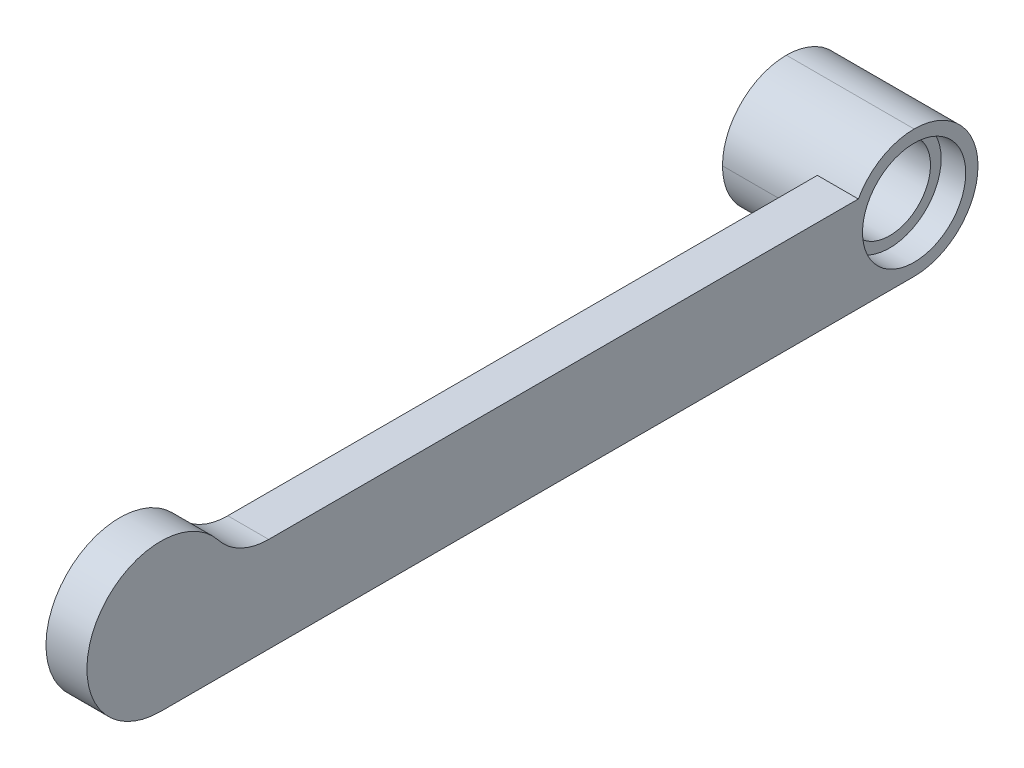
SolidWorks part; units mm, degrees
ref_plane "前视基准面" through (0, 0, 0) normal (0, 0, 1) x (1, 0, 0)
ref_plane "上视基准面" through (0, 0, 0) normal (0, 1, 0) x (1, 0, 0)
ref_plane "右视基准面" through (0, 0, 0) normal (1, 0, 0) x (0, 0, -1)
other "Configuration Table"
sketch "草图1" plane through (0, 0, 0) normal (1, 0, 0) x (0, 0, -1)
  line L0 (46, 3.3) -> (46, -4.5) construction
  line L1 (0, -4.5) -> (49.9, -4.5)
  line L2 (0, -4.5) -> (0, 3.3)
  line L3 (0, 3.3) -> (49.9, 3.3)
  line L4 (49.9, -4.5) -> (49.9, 3.3)
  line L6 (42.1, -4.5) -> (49.9, -4.5)
  line L7 (42.1, -4.5) -> (42.1, 3.3)
  line L8 (42.1, 3.3) -> (49.9, 3.3)
  line L9 (49.9, -4.5) -> (49.9, 3.3)
  line L10 (42.1, -4.5) -> (49.9, 3.3) construction
  line L11 (42.1, 3.3) -> (49.9, -4.5) construction
  circle A4 centre (0, 0) radius 1.8
  circle A5 centre (0, 0) radius 4.5
  circle A6 centre (46, -0.6) radius 2.5
  circle A7 centre (46, -0.6) radius 3.15
  circle A8 centre (0, 0) radius 0.25
  point P9 (46, -0.6)
  dimension "D1" = 3.6
  dimension "D4" = 46
  dimension "D5" = 3.9
  dimension "D2" = 9
  dimension "D6" = 5
  dimension "D7" = 6.3
  dimension "D8" = 0.5
  dimension "D3" = 7.8
extrude "凸台-拉伸1" add sketch "草图1" along normal blind 2.5 contours A5 | L3 L4 L1 L2
extrude "凸台-拉伸3" add sketch "草图1<6>" along normal blind 1.5 from surface contours L2 A4 | L2 A4 region at (0, 0, 0.7769) region at (0, 0, -0.7769) starting at face at (2.5, -0.0392, -24.2851)
sketch "草图1<6>" plane through (0, 0, 0) normal (1, 0, 0) x (0, 0, -1) same geometry as "草图1"
extrude "凸台-拉伸2" add sketch "草图1<5>" along normal blind 7.8 contours A6 | A7 A6 | L7 L1 L4 L3 A7 region at (0, -0.6, -42.2103) region at (0, -0.6, -46) region at (0, -0.6, -42.9391)
sketch "草图1<5>" plane through (0, 0, 0) normal (1, 0, 0) x (0, 0, -1) same geometry as "草图1"
extrude "切除-拉伸1" cut sketch "草图1<7>" along normal through all contours A6 region at (0, -0.6, -46)
sketch "草图1<7>" plane through (0, 0, 0) normal (1, 0, 0) x (0, 0, -1) same geometry as "草图1"
extrude "切除-拉伸2" cut sketch "草图1<8>" along normal blind 1.5 contours A7 A6 region at (0, -0.6, -42.9391)
sketch "草图1<8>" plane through (0, 0, 0) normal (1, 0, 0) x (0, 0, -1) same geometry as "草图1"
extrude "切除-拉伸3" cut sketch "草图1<9>" against normal blind 1.5 from surface contours A7 A6 region at (0, -0.6, -42.9391) starting at face at (7.8, -0.6, -48.5)
sketch "草图1<9>" plane through (0, 0, 0) normal (1, 0, 0) x (0, 0, -1) same geometry as "草图1"
sketch "草图2" plane through (0, 0, 0) normal (-1, 0, 0) x (0, 0, 1)
  line L0 (-3.0594, 3.3) -> (-49.9, 3.3) construction
  line L1 (-42.1, 3.3) -> (-4.5, 3.3)
  line L2 (-42.1, 3.3) -> (-42.1, 1.3)
  line L3 (-42.1, 1.3) -> (-4.5, 1.3)
  line L4 (-4.5, 3.3) -> (-4.5, 1.3)
  line L5 (-42.1, 3.3) -> (-42.1, -4.5) construction
  line L6 (-4.5, 3.3) -> (-3.0594, 3.3)
  line L8 (-4.5, 1.3) -> (-4.3081, 1.3)
  line L9 (-4.5, 1.3) -> (-4.5, 3.3)
  line L10 (-4.5, 3.3) -> (-4.3081, 3.3)
  line L11 (-4.3081, 1.3) -> (-4.3081, 3.3)
  arc A1 (0, -4.5) -> (-3.0594, 3.3) centre (0, 0) ccw construction
  circle A2 centre (0, 0) radius 4.5
  line M7 (-3.0594, 3.3) -> (-49.9, 3.3)
  dimension "D1" = 2
extrude "切除-拉伸4" cut sketch "草图2" against normal through all contours A2 L11 M7 | L8 L11 L6 L4 | L4 L2 L3 M7 region at (0, 2.3, -23.3) region at (0, 2.3, -4.4041) region at (0, 2.7076, -3.9302)
fillet "圆角1" radius 3.9 5 edges at (3.9, -4.5, -49.9) (3.9, 3.3, -49.9) (5.15, -4.5, -42.1) (3.9, 3.3, -42.1) (1.25, 1.3, -4.3081)
ref_plane "基准面1" through (-1, 0, 0) normal (-1, 0, 0) x (0, 0, 1)
mirror "镜向2" about plane through (-1, 0, 0) normal (-1, 0, 0) of bodies 118 114
sketch "草图3" plane through (-4.5, 0, 0) normal (0, -1, 0) x (0, 0, 1)
  line L1 (-55.5542, 7.4344) -> (21.7164, 7.4344)
  line L2 (-55.5542, 7.4344) -> (-55.5542, -3.5409)
  line L3 (-55.5542, -3.5409) -> (21.7164, -3.5409)
  line L4 (21.7164, 7.4344) -> (21.7164, -3.5409)
extrude "切除-拉伸5" cut sketch "草图3" against normal through all both and the other way through all flip side to cut
